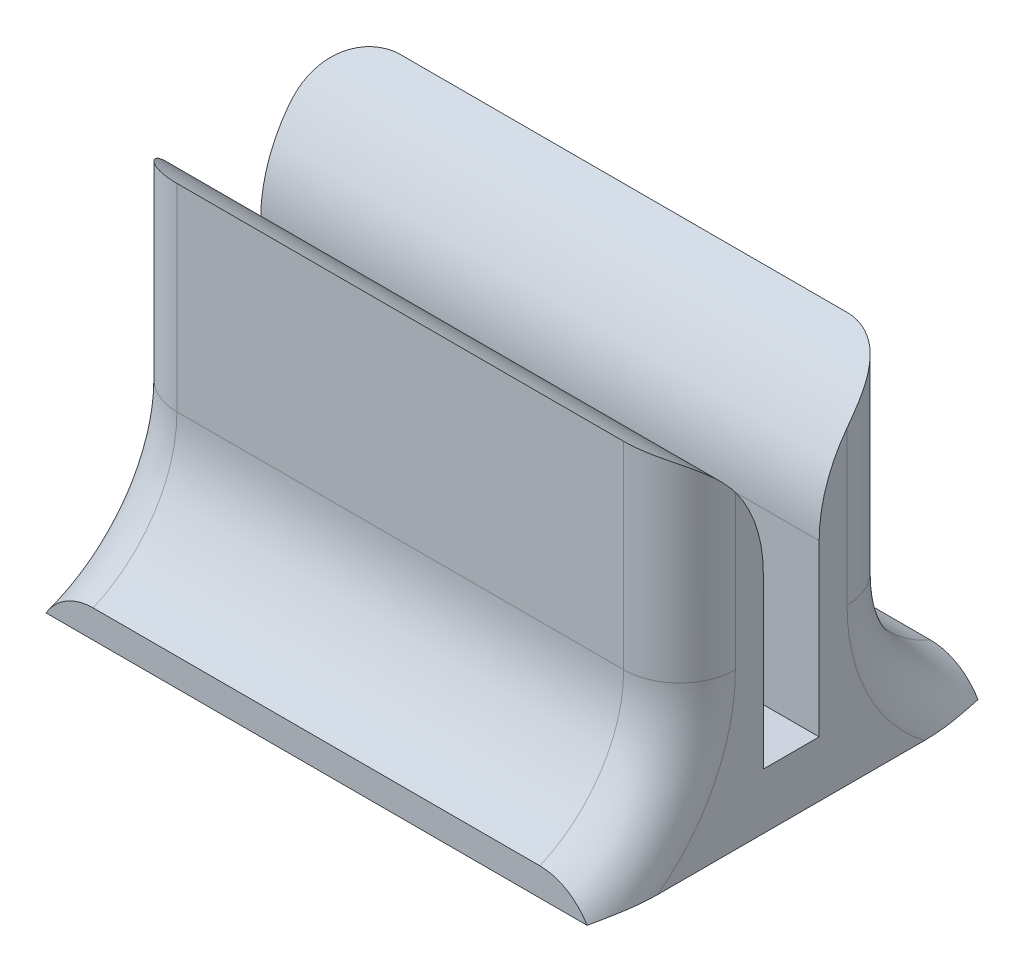
SolidWorks part; units mm, degrees
material "ABS PC"
ref_plane "Front Plane" through (0, 0, 0) normal (0, 0, 1) x (1, 0, 0)
ref_plane "Top Plane" through (0, 0, 0) normal (0, 1, 0) x (1, 0, 0)
ref_plane "Right Plane" through (0, 0, 0) normal (1, 0, 0) x (0, 0, -1)
other "Center of Mass"
sketch "Sketch2" plane through (0, 0, 0) normal (0, 1, 0) x (1, 0, 0)
  line L0 (-50, 0) -> (50, 0) construction
  line L2 (-50, 20) -> (50, 20)
  line L3 (-50, 20) -> (-50, -20)
  line L4 (-50, -20) -> (50, -20)
  line L5 (50, 20) -> (50, -20)
  line L6 (-50, 20) -> (50, -20) construction
  line L7 (-50, -20) -> (50, 20) construction
  point P5 (0, 0)
  dimension "D1" = 100
  dimension "D2" = 40
extrude "Boss-Extrude1" add sketch "Sketch2" along normal blind 10
sketch "Sketch4" plane through (0, 0, 0) normal (0, 1, 0) x (1, 0, 0)
  line L0 (-55, 0) -> (55, 0) construction
  line L5 (50, -20) -> (50, 20) construction
  line L6 (-50, -20) -> (50, -20)
  line L7 (0, 5) -> (0, -5) construction
  line L8 (0, -55) -> (0, 55) construction
  line L9 (-50, 5) -> (50, 20) construction
  line L10 (-50, 20) -> (50, 5) construction
  line L11 (50, 20) -> (50, 5)
  line L16 (-50, -20) -> (-50, -5)
  line L17 (-50, -5) -> (50, -5)
  line L18 (50, -20) -> (50, -5)
  line L19 (-50, -20) -> (50, -5) construction
  line L20 (-50, -5) -> (50, -20) construction
  line L21 (-50, 5) -> (50, 5)
  line L22 (-50, 20) -> (-50, 5)
  line L23 (-50, 20) -> (50, 20)
  point P4 (0, -23.5)
  point P6 (0, -12.5)
  point P8 (0, 12.5)
  point P21 (0, 0)
  point P22 (0, 23.5)
  dimension "D1" = 5
extrude "Boss-Extrude2" add sketch "Sketch4" along normal blind 63.3333
fillet "Fillet1" radius 25 1 edges at (0, 63.3333, 5)
fillet "Fillet2" radius 25 1 edges at (0, 63.3333, -5)
sketch "Sketch5" plane through (0, 0, 0) normal (0, 1, 0) x (1, 0, 0)
  line L0 (-50, -20) -> (50, -20) construction
  line L1 (-50, -20) -> (50, -20)
  line L2 (-50, -20) -> (-50, -35)
  line L3 (-50, -35) -> (50, -35)
  line L4 (50, -20) -> (50, -35)
  line L5 (-50, -20) -> (50, -35) construction
  line L6 (-50, -35) -> (50, -20) construction
  line L7 (-55, 0) -> (55, 0) construction
  line L8 (-50, 35) -> (50, 20) construction
  line L9 (-50, 20) -> (50, 35) construction
  line L10 (50, 20) -> (50, 35)
  line L11 (-50, 35) -> (50, 35)
  line L12 (-50, 20) -> (-50, 35)
  line L13 (-50, 20) -> (50, 20)
  point P4 (0, -27.5)
  point P14 (0, 27.5)
  dimension "D1" = 15
extrude "Boss-Extrude3" add sketch "Sketch5" along normal blind 5
fillet "Fillet3" radius 25 1 edges at (0, 5, 20)
fillet "Fillet4" radius 25 1 edges at (0, 5, -20)
fillet "Fillet10" radius 10 2 edges at (-50, 14.2198, -24.0835) (-50, 45.6231, -20)
fillet "Fillet11" radius 10 6 edges at (50, 14.2198, -24.0835) (50, 14.2198, 24.0835) (-50, 14.2198, 24.0835) (50, 45.6231, -20) (50, 45.6231, 20) (-50, 45.6231, 20)
sketch "Sketch9" plane through (0, 0, 0) normal (0, 1, 0) x (1, 0, 0)
  line L0 (0, -55) -> (0, 55) construction
  line L1 (-65, 19) -> (65, 19)
  line L2 (-65, 19) -> (-65, 6)
  line L3 (-65, 6) -> (65, 6)
  line L4 (65, 19) -> (65, 6)
  line L5 (-65, 19) -> (65, 6) construction
  line L6 (-65, 6) -> (65, 19) construction
  line L7 (-55, 0) -> (55, 0) construction
  line L8 (-65, -6) -> (65, -19) construction
  line L9 (-65, -19) -> (65, -6) construction
  line L10 (65, -19) -> (65, -6)
  line L11 (-65, -6) -> (65, -6)
  line L12 (-65, -19) -> (-65, -6)
  line L13 (-65, -19) -> (65, -19)
  point P4 (0, 12.5)
  point P14 (0, -12.5)
  dimension "D1" = 130
  dimension "D2" = 13
equation "\"ipadlength\"= 10"
equation "\"ipadheight\" = 18"
equation "\"ipadwidth\"= 1cm"
equation "\"D1@Sketch4\"=\"ipadwidth\"*1/2"
equation "\"D1@Sketch5\"=\"ipadwidth\"*1.5"
